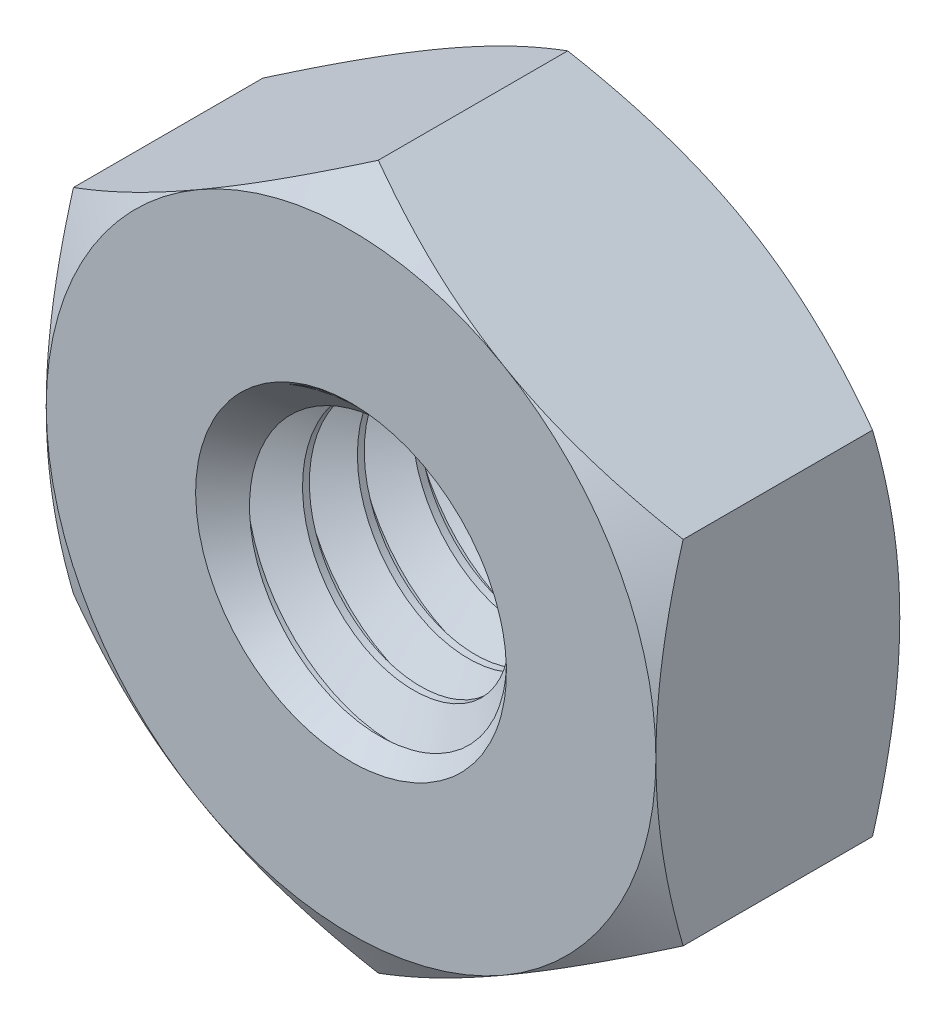
SolidWorks part; units mm, degrees
material "Plain Carbon Steel"
ref_plane "Front Plane" through (0, 0, 0) normal (0, 0, 1) x (1, 0, 0)
ref_plane "Top Plane" through (0, 0, 0) normal (0, 1, 0) x (1, 0, 0)
ref_plane "Right Plane" through (0, 0, 0) normal (1, 0, 0) x (0, 0, -1)
sketch "Sketch1" plane through (0, 0, 0) normal (1, 0, 0) x (0, 0, -1)
  line L0 (-1, 0) -> (1, 0) construction
  line L1 (-1, -2.5) -> (-1, 2.5) construction
  line L2 (1, -2.5) -> (1, 2.5) construction
  line L3 (-1, -1.25) -> (-1, 1.25) construction
  line L4 (-1.4219, 1.2987) -> (-1.1969, 0.909) construction
  line L5 (-1.1969, 0.909) -> (-0.9719, 1.2987) construction
  line L6 (-0.9719, 1.2987) -> (-1.4219, 1.2987) construction
  line L7 (-1.4078, 1.2744) -> (-0.9859, 1.2744) construction
  line L8 (-1.3938, 1.25) -> (-1, 1.25) construction
  line L9 (-1.225, 0.9577) -> (-1.1688, 0.9577) construction
  line L10 (-1.1969, 0.9577) -> (-1.1969, 0.909) construction
  line L11 (-1.1969, 1.2987) -> (-1.1969, 1.25) construction
  point P4 (0, 0)
  point P7 (-1, 0)
  point P11 (1, 0)
  point P14 (-1, 0)
  point P26 (-1.1969, 1.2744)
  point P27 (-1, -1.25)
  dimension "Height" = 2
  dimension "Width" = 5
  dimension "Thread OD" = 2.5
  dimension "D1" = 60
  dimension "Pitch" = 0.45
  dimension "D2" = 0.0563
sketch "Sketch2" plane through (0, 0, 0) normal (0, 0, 1) x (1, 0, 0)
  line L1 (0, 2.8868) -> (-2.5, 1.4434)
  line L2 (-2.5, 1.4434) -> (-2.5, -1.4434)
  line L3 (-2.5, -1.4434) -> (0, -2.8868)
  line L4 (0, -2.8868) -> (2.5, -1.4434)
  line L5 (2.5, -1.4434) -> (2.5, 1.4434)
  line L6 (2.5, 1.4434) -> (0, 2.8868)
  circle A0 centre (0, 0) radius 2.5 construction
  circle A1 centre (0, 0) radius 1.25
extrude "Boss-Extrude1" add sketch "Sketch2" along normal up to vertex (1 mm away) and the other way up to vertex (1 mm away) up to point (0, -2.5, 1) other way up to point (0, -2.5, -1)
sketch "Sketch3" plane through (0, 0, 1) normal (0, 0, 1) x (1, 0, 0)
  circle A0 centre (0, 0) radius 2.5
extrude "Cut-Extrude1" cut sketch "Sketch3" against normal through all draft 60 flip side to cut
mirror "Mirror1" about plane through (0, 0, 0) normal (0, 0, 1) of "Cut-Extrude1"
ref_axis "Center Axis 1" through (0, 0, -10.9016) along (0, 0, 1)
ref_plane "Contact Plane 1" through (0, 0, 1) normal (0, 0, 1) x (1, 0, 0)
ref_plane "Contact Plane 2" through (0, 0, -1) normal (0, 0, -1) x (-1, 0, 0)
sketch "Sketch4" plane through (0, 0, 0) normal (1, 0, 0) x (0, 0, -1)
  line L1 (-1.4078, 1.2744) -> (-1.225, 0.9577)
  line L2 (-1.225, 0.9577) -> (-1.1688, 0.9577)
  line L3 (-1.1688, 0.9577) -> (-0.9859, 1.2744)
  line L4 (-1.4078, 1.2744) -> (-0.9859, 1.2744) construction
  line L5 (-1.4078, 1.2744) -> (-0.9859, 1.2744)
sketch "Sketch5" plane through (0, 0, 1) normal (0, 0, 1) x (1, 0, 0)
  circle A0 centre (0, 0) radius 1.25 construction
  circle A1 centre (0, 0) radius 1.25
curve "Helix/Spiral1" pitch 0.45 height 2.45 radius 1.25 centre (0, 0, 1) axis (0, 0, -1) start towards (0, 1, 0)
sweep "Sweep1" add profiles "Sketch4" path "Helix/Spiral1"
sketch "Sketch6" plane through (0, 0, 1) normal (0, 0, 1) x (1, 0, 0)
  circle A1 centre (0, 0) radius 1.2744
extrude "Cut-Extrude2" cut sketch "Sketch6" along normal through all and the other way through all draft 45
sketch "Sketch7" plane through (0, 0, -1) normal (0, 0, -1) x (-1, 0, 0)
  circle A1 centre (0, 0) radius 1.2744
  circle A2 centre (0, 0) radius 1.2744
  dimension "D1" = 0
extrude "Cut-Extrude3" cut sketch "Sketch7" along normal through all and the other way through all draft 45
equation "\"D2@Sketch1\"=\"Pitch@Sketch1\"/8"
equation "\"D4@Helix/Spiral1\"=\"Pitch@Sketch1\""
equation "\"D3@Helix/Spiral1\"=\"Height@Sketch1\"+\"Pitch@Sketch1\""
